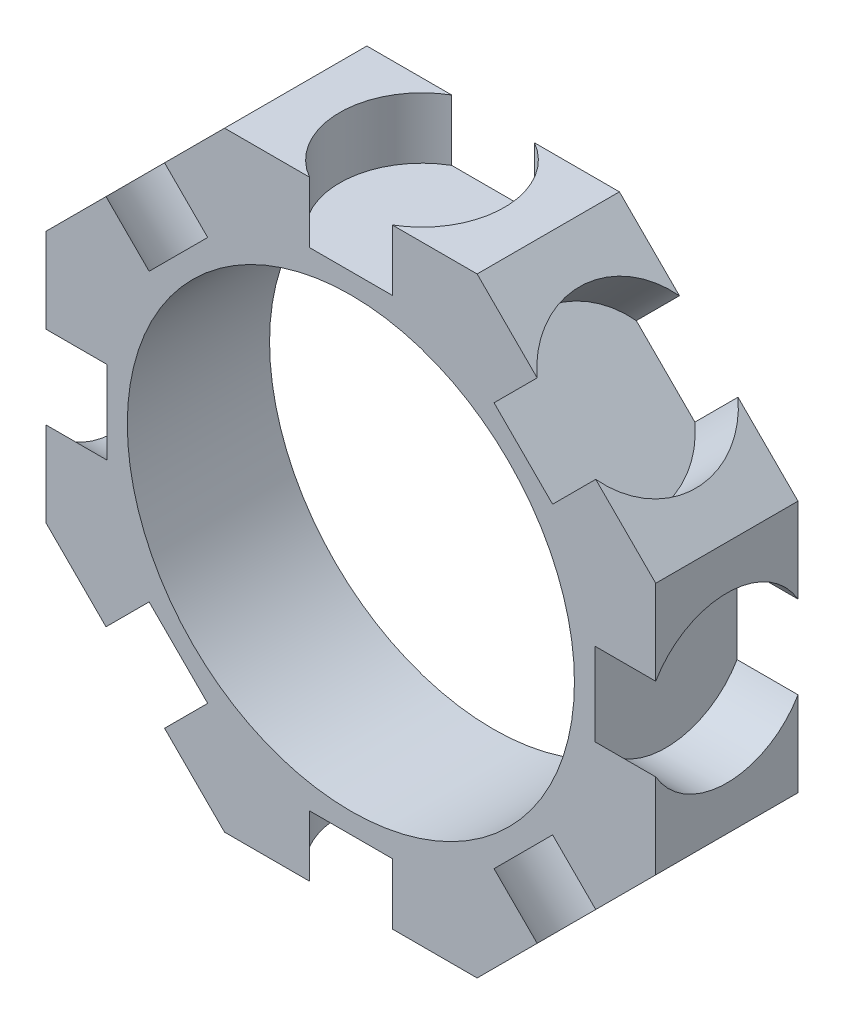
SolidWorks part; units mm, degrees
ref_plane "Top Plane" through (0, 0, 0) normal (0, 0, 1) x (1, 0, 0)
ref_plane "Right Plane" through (0, 0, 0) normal (0, 1, 0) x (1, 0, 0)
ref_plane "Front Plane" through (0, 0, 0) normal (1, 0, 0) x (0, 0, -1)
ref_axis "x-axis" through (-88.99, 0, 0) along (1, 0, 0)
ref_axis "y-axis" through (0, -55, 0) along (0, 1, 0)
ref_axis "z-axis" through (0, 0, 55) along (0, 0, -1)
sketch "Sketch1" plane through (0, 0, 0) normal (0, 0, 1) x (1, 0, 0)
  line L0 (6.2132, 15) -> (-6.2132, 15)
  line L1 (-15, 6.2132) -> (-15, -6.2132)
  line L2 (-15, -6.2132) -> (-6.2132, -15)
  line L3 (-6.2132, -15) -> (6.2132, -15)
  line L4 (6.2132, -15) -> (15, -6.2132)
  line L5 (15, -6.2132) -> (15, 6.2132)
  line L6 (15, 6.2132) -> (6.2132, 15)
  line L7 (-6.2132, 15) -> (-15, 6.2132)
  line L8 (-15, 0) -> (0, 0) construction
  circle A0 centre (0, 0) radius 11
  circle A1 centre (0, 0) radius 15 construction
  dimension "D1" = 22
  dimension "D2" = 15
extrude "Boss-Extrude1" add sketch "Sketch1" along normal mid plane 7
sketch "Sketch2" plane through (0, -15, 0) normal (0, -1, 0) x (-1, 0, 0)
  circle A0 centre (0, 0) radius 4.05
  dimension "D1" = 8.1
extrude "Cut-Extrude3" cut sketch "Sketch2" against normal blind 3
pattern_circular "CirPattern1" count 8 over 360 about axis through (0, 0, 3.5) along (0, 0, 1) of "Cut-Extrude3"
